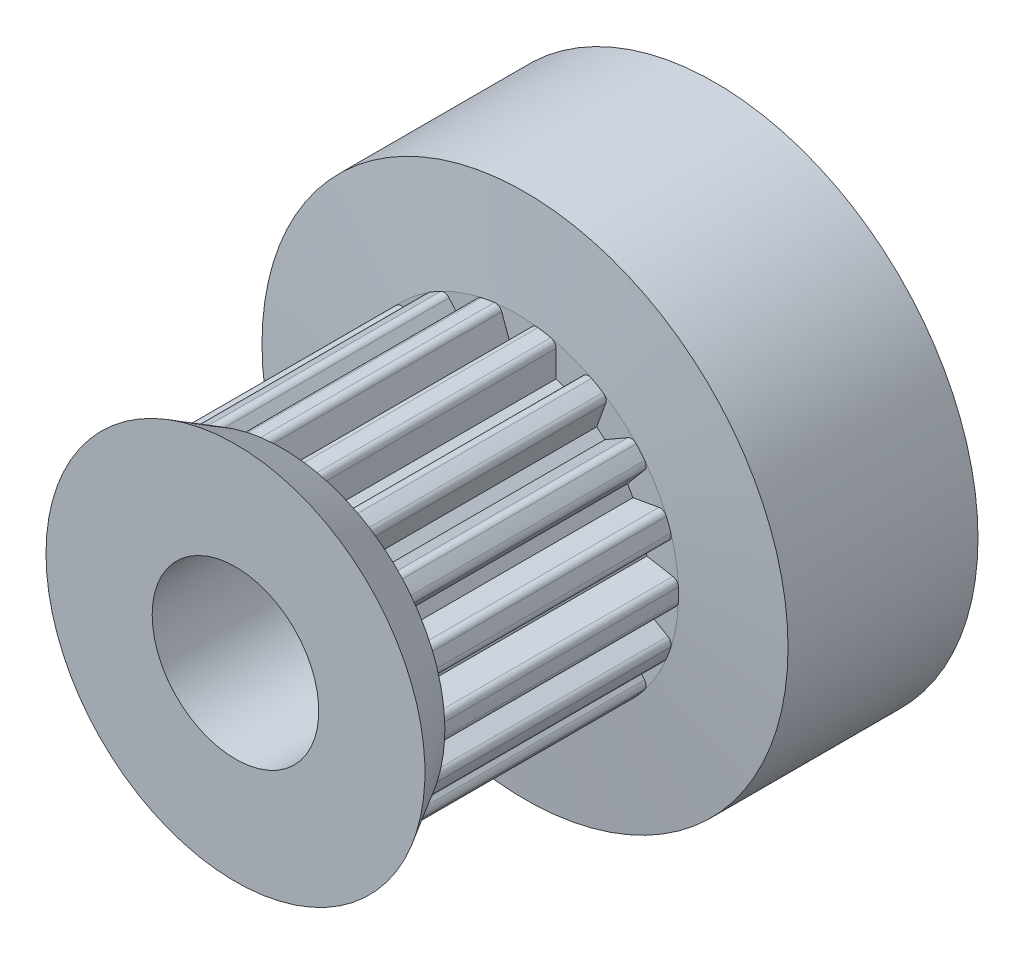
SolidWorks part; units mm, degrees
material "ABS"
ref_plane "Front Plane" through (0, 0, 0) normal (0, 0, 1) x (1, 0, 0)
ref_plane "Top Plane" through (0, 0, 0) normal (0, 1, 0) x (1, 0, 0)
ref_plane "Right Plane" through (0, 0, 0) normal (1, 0, 0) x (0, 0, -1)
sketch "Sketch8" plane through (0, 0, 0) normal (1, 0, 0) x (0, 0, -1)
  line L0 (7.5979, 0) -> (-14.162, 0) construction
  line L1 (10.8016, -2.85) -> (10.8016, -9)
  line L2 (4, -5.5563) -> (-4, -5.5563)
  line L3 (-5.606, -6.4835) -> (-4, -5.5563)
  line L4 (10.8016, -9) -> (4.3016, -9)
  line L5 (-5.606, -6.4835) -> (-5.606, -2.85)
  line L6 (4, -5.5563) -> (4.3016, -9)
  line L7 (0, 0) -> (0, -5.5563) construction
  line L13 (10.8016, -2.85) -> (-5.606, -2.85)
  dimension "D1" = 2.85
  dimension "D2" = 6.5
  dimension "D3" = 9
  dimension "D4" = 5.5563
  dimension "D5" = 30
  dimension "D6" = 8
revolve "Revolve1" add sketch "Sketch8" angle 360 about L0
sketch "Sketch7" plane through (0, 0, 0) normal (0, 0, 1) x (1, 0, 0)
  line L0 (0, 0) -> (0, 11.2147) construction
  line L1 (-0.7424, 5.5064) -> (0.7424, 5.5064) construction
  line L2 (-0.1859, 4.5064) -> (0.1859, 4.5064)
  line L9 (0.1859, 4.5064) -> (0.4955, 5.3572)
  line L11 (-0.1859, 4.5064) -> (-0.4955, 5.3572)
  arc A0 (0.7424, 5.5064) -> (0.4955, 5.3572) centre (0.7116, 5.2785) ccw
  circle A1 centre (0, 0) radius 5.5563 construction
  arc A4 (-0.4955, 5.3572) -> (-0.7424, 5.5064) centre (-0.7116, 5.2785) ccw
  arc A6 (0.7424, 5.5064) -> (-0.7424, 5.5064) centre (0, 0) ccw
  point P6 (0, 4.5064)
  point P12 (0, 5.5064)
  dimension "D3" = 0.23
  dimension "D4" = 0.23
  dimension "D2" = 0.991
  dimension "D1" = 40
  dimension "D5" = 1
extrude "Cut-Extrude1" cut sketch "Sketch7" against normal blind 4 and the other way blind 4
pattern_circular "CirPattern1" count 18 over 360 about axis through (0, 0, -7.5979) along (0, 0, -1) of "Cut-Extrude1"
sketch "Sketch9" plane through (0, 0, 0) normal (1, 0, 0) x (0, 0, -1)
  line L0 (0, 0) -> (15.7339, 0) construction
  line L1 (7.5516, 9) -> (7.5516, -9) construction
  line L2 (10.8016, -9) -> (10.8016, 9) construction
  line L3 (10.8016, 3) -> (5.8196, 3)
  line L4 (5.8196, 3) -> (4.0875, 0)
  line L5 (4.0875, 0) -> (5.8196, -3)
  line L6 (5.8196, -3) -> (10.8016, -3)
  line L7 (10.8016, 3) -> (10.8016, -3)
  line L8 (10.8016, 9) -> (4.3016, 9) construction
  line L9 (4.3016, -9) -> (10.8016, -9) construction
  line L11 (11.0157, 0) -> (9.2837, 3) [skipped]
  line L12 (9.2837, -3) -> (11.0157, 0) [skipped]
  circle A0 centre (7.5516, 0) radius 1.5
  circle A1 centre (7.5516, 0) radius 3 construction
  dimension "D1" = 3
  dimension "D2" = 6
extrude "Cut-Extrude2" cut sketch "Sketch9" against normal through all contours A0 region at (0, 0, -7.5516)
extrude "Cut-Extrude3" cut sketch "Sketch9<3>" against normal blind 5.85
sketch "Sketch9<3>" plane through (0, 0, 0) normal (1, 0, 0) x (0, 0, -1) same geometry as "Sketch9"
equation "\"rod_diameter\"= 8"
equation "\"rod_hole_thickness\"= 4"
equation "\"rod_radius\"= \"rod_diameter\" / 2"
equation "\"platter_diameter\"= 320"
equation "\"platter_radius\"= \"platter_diameter\" / 2"
equation "\"extruder_mount_hole_spacing\"= 75"
equation "\"arm_rod_spacing\"= 40"
equation "\"top_frame_spacing\"= 90"
equation "\"motor_level_rod_spacing\"= 15"
equation "\"linear_bearing_diameter\"= 15"
equation "\"z_rod_spacing\"= 75"
equation "\"platter_rod_spacing\"= 50"
equation "\"rod_nut_thickness\"= 6.5"
equation "\"rod_nut_inscribed_diameter\"= 13"
equation "\"z_height\"= 350"
equation "\"gear_pitch\"=2"
equation "\"r_gear_teeth\"= 450"
equation "\"theta_gear_teeth\"= 385"
equation "\"sheet_thickness\"=5"
equation "\"sheet_tab_hole_thickness\"= \"sheet_thickness\""
equation "\"sheet_tab_width\"= \"sheet_thickness\"*2"
equation "\"sheet_bolt_diameter\"= 3"
equation "\"sheet_bolt_length\"= 16"
equation "\"sheet_nut_diameter\"= 5.5"
equation "\"sheet_nut_thickness\"= 2.5"
equation "\"sheet_nut_depth\"= 10"
equation "\"bearing_outside_diameter\"= 22"
equation "\"bearing_thickness\"= 7"
equation "\"corner_part_thickness\"= \"sheet_thickness\" + \"bearing_thickness\""
equation "\"setscrew_nut_diameter\"= 6"
equation "\"setscrew_nut_thickness\"= 3"
equation "\"setscrew_bolt_diameter\"= 3"
equation "\"D1@Sketch9\"=\"setscrew_bolt_diameter\""
equation "\"D2@Sketch9\"=\"setscrew_nut_diameter\""
equation "\"motor_shaft_diameter\"= 5.7"
equation "\"D1@Sketch8\"=\"motor_shaft_diameter\"/2"
equation "\"D1@Cut-Extrude3\"= \"motor_shaft_diameter\" / 2 + \"setscrew_nut_thickness\""
